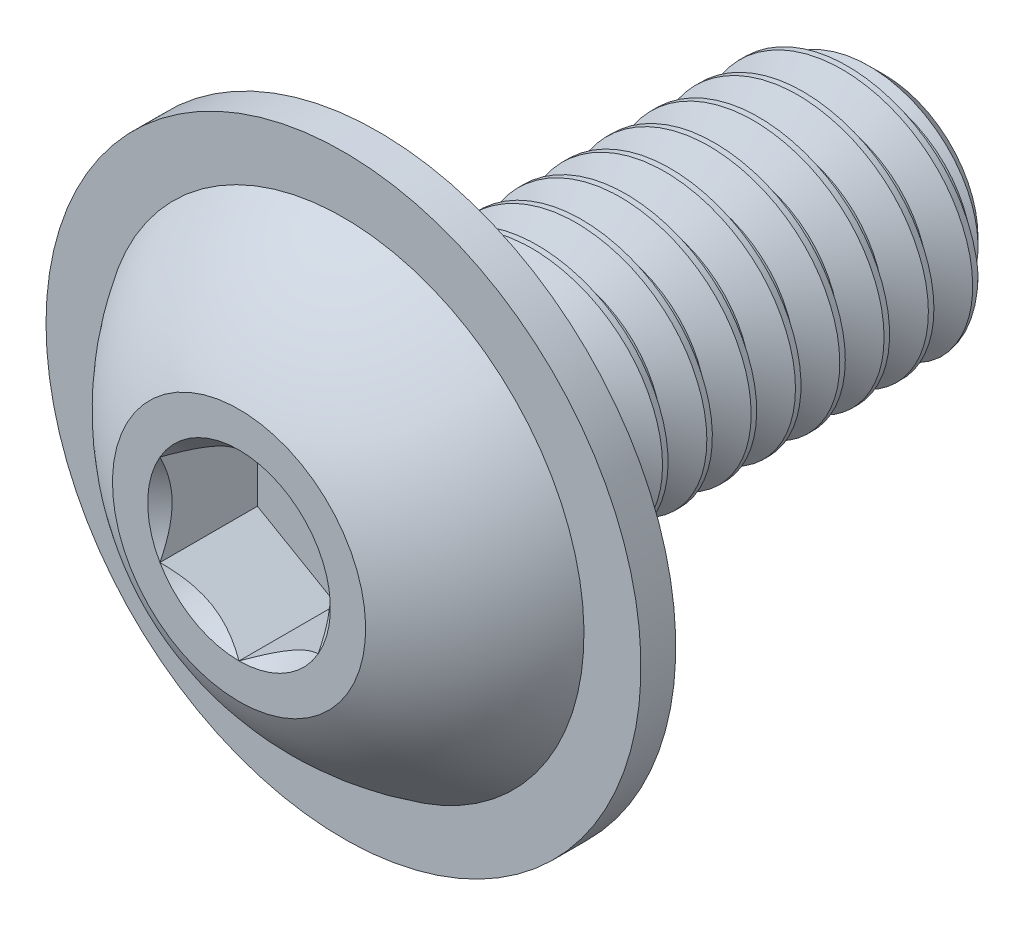
SolidWorks part; units mm, degrees
ref_plane "Front" through (0, 0, 0) normal (0, 0, 1) x (1, 0, 0)
ref_plane "Top" through (0, 0, 0) normal (0, 1, 0) x (1, 0, 0)
ref_plane "Right" through (0, 0, 0) normal (1, 0, 0) x (0, 0, -1)
sketch "Sketch1" plane through (0, 0, 0) normal (1, 0, 0) x (0, 0, -1)
  line L2 (2.2, 2) -> (10.2, 2)
  line L3 (10.2, 2) -> (10.2, 0)
  line L4 (10.2, 0) -> (2.2, 0)
  line L6 (1.65, 3.8) -> (2.2, 3.8) construction
  line L7 (10.2, 2) -> (10.2, -2) construction
  line L8 (0, 0) -> (2.2, 0) construction
  line L9 (2.2, 3.8) -> (2.2, -3.8) construction
  line L11 (2.2, 2) -> (2.2, 0)
  line L13 (0, 1.25) -> (0, -1.25) construction
  line L14 (0, 1.25) -> (0, 2) construction
  line L15 (1.65, 3.8) -> (1.65, 4.7) construction
  line L16 (1.65, 4.7) -> (2.2, 4.7) construction
  line L17 (2.2, 4.7) -> (2.2, 3.8) construction
  line L18 (2.2, 4.7) -> (2.2, -4.7) construction
  arc A3 (0, 2) -> (1.65, 3.8) centre (3.9886, 0) cw construction
  dimension "D1" = 0.55
revolve "Revolve1" add sketch "Sketch1" angle 360 mid plane about L4
sketch "Sketch3" plane through (0, 0, -10.2) normal (0, 0, -1) x (-1, 0, 0)
  circle A0 centre (0, 0) radius 2
chamfer "Chamfer1" distance 0.525 angle 45 1 edges at (0, 2, -10.2)
sketch "Sketch7" plane through (0, 0, 0) normal (1, 0, 0) x (0, 0, -1)
  line L6 (1.65, 3.8) -> (2.2, 3.8) construction
  line L8 (0, 0) -> (2.2, 0) construction
  line L11 (2.2, 3.8) -> (2.2, -3.8) construction
  line L12 (1.65, 3.8) -> (2.2, 3.8)
  line L13 (0, 0) -> (2.2, 0)
  line L14 (0, 1.25) -> (0, -1.25) construction
  line L15 (2.2, 3.8) -> (2.2, 0)
  line L16 (0, 2) -> (0, 0)
  arc A2 (1.65, 3.8) -> (0, 2) centre (3.9886, 0) ccw construction
  arc A3 (1.65, 3.8) -> (0, 2) centre (3.9886, 0) ccw
revolve "Revolve2" add sketch "Sketch7" angle 360 mid plane about L13
sketch "Sketch11" plane through (0, 0, -2.2) normal (0, 0, -1) x (-1, 0, 0)
  circle A0 centre (0, 0) radius 4.7
extrude "Boss-Extrude3" add sketch "Sketch11" against normal up to vertex (0.55 mm away) up to point (0, 3.8, -1.65)
sketch "Sketch5" plane through (0, 0, 0) normal (0, 0, 1) x (1, 0, 0)
  line L1 (1.25, -0.7217) -> (1.25, 0.7217)
  line L2 (1.25, 0.7217) -> (0, 1.4434)
  line L3 (0, 1.4434) -> (-1.25, 0.7217)
  line L4 (-1.25, 0.7217) -> (-1.25, -0.7217)
  line L5 (-1.25, -0.7217) -> (0, -1.4434)
  line L6 (0, -1.4434) -> (1.25, -0.7217)
  circle A0 centre (0, 0) radius 1.25 construction
extrude "Cut-Extrude2" cut sketch "Sketch5" against normal blind 1.54
sketch "Sketch6" plane through (0, 0, 0) normal (0, 0, 1) x (1, 0, 0)
  circle A0 centre (0, 0) radius 1.4434
extrude "Cut-Extrude3" cut sketch "Sketch6" against normal blind 1.54 draft 45
sketch "Sketch10" plane through (0, 0, 0) normal (1, 0, 0) x (0, 0, -1)
  line L0 (10.2, 2) -> (10.2, -2) construction
  point P0 (8.45, -2)
  dimension "D1" = 1.75
curve "Helix/Spiral1" pitch 0.7 height 8.7 radius 2 centre (0, 0, -10.2) axis (0, 0, 1) start towards (0, 1, 0)
sketch "Sketch2" plane through (0, 0, 0) normal (1, 0, 0) x (0, 0, -1)
  line L0 (10.2, 2) -> (10.8125, 2)
  line L1 (10.8125, 2) -> (10.55, 1.5453)
  line L2 (10.55, 1.5453) -> (10.4625, 1.5453)
  line L3 (10.4625, 1.5453) -> (10.2, 2)
  line L4 (10.3313, 1.7727) -> (10.6813, 1.7727) construction
  dimension "D1" = 60
  dimension "D2" = 0.0875
  dimension "D3" = 0.35
sweep "Cut-Sweep1" cut profiles "Sketch2" path "Helix/Spiral1" align with end faces yes
sketch "Sketch12" plane through (0, 0, -2.2) normal (0, 0, -1) x (-1, 0, 0)
  circle A1 centre (0, 0) radius 2
  circle A2 centre (0, 0) radius 2
  dimension "D1" = 0
extrude "Boss-Extrude4" add sketch "Sketch12" along normal up to next (8 mm away) draft 20
ref_axis "Center Axis 1" through (0, 0, -12.2069) along (0, 0, 1)
ref_plane "Contact Plane 1" through (0, 0, -2.2) normal (0, 0, -1) x (-1, 0, 0)
equation "\"D3@Helix/Spiral1\" = \"Lg@Sketch1\" + \"D4@Helix/Spiral1\""
equation "\"D2@Sketch2\" = \"D4@Helix/Spiral1\" * .125"
equation "\"D3@Sketch2\" = \"D4@Helix/Spiral1\" * .5"
equation "\"D1@Chamfer1\" = \"D4@Helix/Spiral1\" * .75"
equation "\"D1@Cut-Extrude2\" = \"Head Ht@Sketch1\" * .7"
equation "\"D1@Sketch1\" = \"Head Ht@Sketch1\" * .25"
equation "\"D1@Sketch10\"=\"D4@Helix/Spiral1\" * 2.5"
equation "\"D1@Cut-Extrude3\" = \"D1@Cut-Extrude2\""
